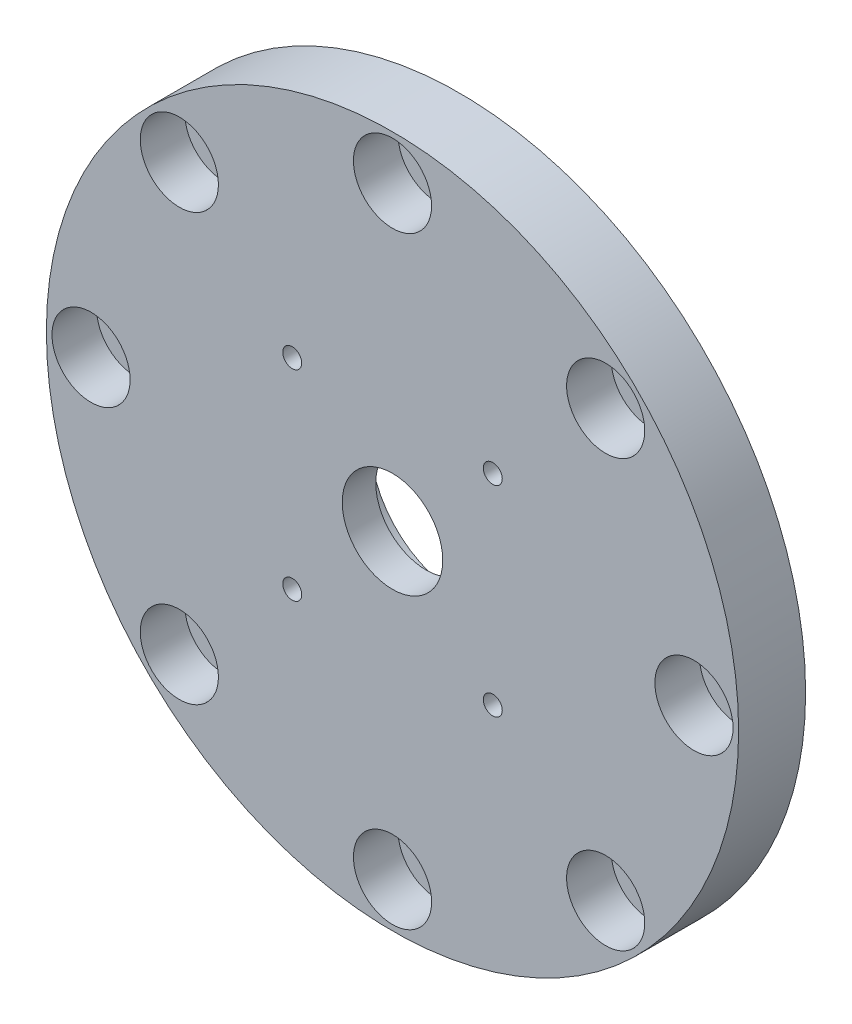
SolidWorks part; units mm, degrees
ref_plane "Front Plane" through (0, 0, 0) normal (0, 0, 1) x (1, 0, 0)
ref_plane "Top Plane" through (0, 0, 0) normal (0, 1, 0) x (1, 0, 0)
ref_plane "Right Plane" through (0, 0, 0) normal (1, 0, 0) x (0, 0, -1)
sketch "Sketch1" plane through (0, 0, 0) normal (0, 0, 1) x (1, 0, 0)
  line L11 (0, 0) -> (8.9803, 8.9803) construction
  line L17 (0, 0) -> (-27, 0) construction
  circle A2 centre (0, 0) radius 4.5
  circle A3 centre (0, 0) radius 12.7 construction
  circle A11 centre (8.9803, 8.9803) radius 0.85
  circle A12 centre (8.9803, -8.9803) radius 0.85
  circle A13 centre (-8.9803, -8.9803) radius 0.85
  circle A14 centre (-8.9803, 8.9803) radius 0.85
  circle A33 centre (0, 0) radius 24 construction
  circle A34 centre (0, 0) radius 31
  circle A35 centre (-27, 0) radius 1.55
  circle A36 centre (-19.0919, 19.0919) radius 1.55
  circle A37 centre (0, 27) radius 1.55
  circle A38 centre (19.0919, 19.0919) radius 1.55
  circle A39 centre (27, 0) radius 1.55
  circle A40 centre (19.0919, -19.0919) radius 1.55
  circle A41 centre (0, -27) radius 1.55
  circle A42 centre (-19.0919, -19.0919) radius 1.55
  point P7 (0, 0)
  point P10 (0, 0)
  point P12 (0, 0)
  point P16 (0, 0)
  point P17 (0, 0)
  point P20 (0, 0)
  point P30 (0, 0)
  point P39 (0, 0)
  point P47 (0, 0)
  point P64 (0, 0)
  dimension "D1" = 4
extrude "Boss-Extrude2" add sketch "Sketch1" along normal blind 6
sketch "Sketch5" plane through (0, 0, 0) normal (0, 0, -1) x (-1, 0, 0)
  circle A0 centre (0, 0) radius 8
extrude "Cut-Extrude3" cut sketch "Sketch5" against normal blind 3
sketch "Sketch6" plane through (0, 0, 6) normal (0, 0, 1) x (1, 0, 0)
  circle A7 centre (0, 27) radius 3.5
  circle A8 centre (19.0919, 19.0919) radius 3.5
  circle A9 centre (27, 0) radius 3.5
  circle A10 centre (19.0919, -19.0919) radius 3.5
  circle A11 centre (0, -27) radius 3.5
  circle A12 centre (-19.0919, -19.0919) radius 3.5
  circle A13 centre (-27, 0) radius 3.5
  circle A14 centre (-19.0919, 19.0919) radius 3.5
  point P11 (-3.75, 3.75)
  point P29 (0, 0)
  point P31 (0, 0)
  dimension "D2" = 8
extrude "Cut-Extrude4" cut sketch "Sketch6" against normal blind 4
